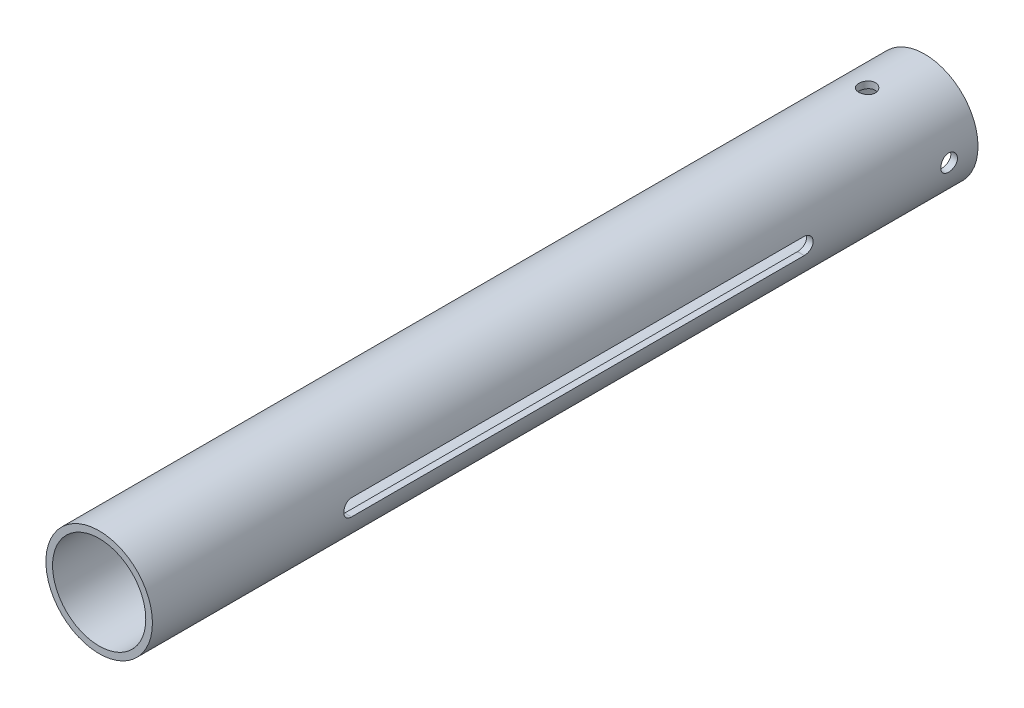
SolidWorks part; units mm, degrees
material "AISI 1010 Steel, hot rolled bar"
ref_plane "Front Plane" through (0, 0, 0) normal (0, 0, 1) x (1, 0, 0)
ref_plane "Top Plane" through (0, 0, 0) normal (0, 1, 0) x (1, 0, 0)
ref_plane "Right Plane" through (0, 0, 0) normal (1, 0, 0) x (0, 0, -1)
sketch "Sketch1" plane through (0, 0, 0) normal (0, 0, 1) x (1, 0, 0)
  line L0 (-25.4, 0) -> (-22.225, 0) construction
  circle A0 centre (0, 0) radius 22.225 construction
  circle A1 centre (0, 0) radius 25.4 construction
  dimension "OD" = 50.8
  dimension "ID" = 44.45
  dimension "Wall Thickness" = 3.175
sketch "Sketch2" plane through (0, 0, 0) normal (1, 0, 0) x (0, 0, -1)
  line L0 (-152.4, -25.4) -> (152.4, -25.4) construction
  point P2 (0, -25.4)
  point P3 (76.2, -25.4)
  point P4 (-76.2, -25.4)
  dimension "Length" = 304.8
  dimension "D1" = 76.2
  dimension "D2" = 76.2
sketch "Sketch3" plane through (0, 0, 0) normal (0, 0, 1) x (1, 0, 0)
  circle A0 centre (0, 0) radius 22.225 construction
  circle A1 centre (0, 0) radius 25.4 construction
  circle A2 centre (0, 0) radius 22.225
  circle A3 centre (0, 0) radius 25.4
extrude "Boss-Extrude2" add sketch "Sketch3" along normal up to vertex (152.4 mm away) and the other way up to vertex (152.4 mm away) up to point (0, -25.4, 152.4) other way up to point (0, -25.4, -152.4)
sketch "Sketch4" plane through (0, 0, 152.4) normal (0, 0, 1) x (1, 0, 0)
  circle A0 centre (0, 0) radius 36.4857
extrude "Cut-Extrude1" [suppressed] cut sketch "Sketch4" against normal offset from surface (12.7 mm away) 12.7 up to face at (25.4, 0, 152.4)
sketch "Sketch9" plane through (0, 0, 152.4) normal (0, 0, 1) x (1, 0, 0)
  circle A0 centre (0, 0) radius 22.225
  circle A1 centre (0, 0) radius 25.4
extrude "Boss-Extrude3" add sketch "Sketch9" along normal blind 88.9
sketch "Sketch5" plane through (0, 0, 0) normal (1, 0, 0) x (0, 0, -1)
  line L0 (-38.1, 0) -> (69.85, 0) construction
  line L1 (-38.1, 0) -> (-146.05, 0) construction
  line L2 (-241.3, 0) -> (152.4, 0) construction
  line L3 (152.4, -25.4) -> (152.4, 25.4) construction
  line L5 (-146.05, 3.9687) -> (69.85, 3.9687)
  line L6 (69.85, -3.9687) -> (-146.05, -3.9687)
  line L7 (-38.1, 3.9687) -> (-38.1, -3.9687) construction
  line L8 (-241.3, 25.4) -> (-241.3, -25.4) construction
  circle A0 centre (-146.05, 0) radius 3.9687 construction
  arc A2 (-146.05, 3.9687) -> (-146.05, -3.9687) centre (-146.05, 0) ccw
  circle A4 centre (69.85, 0) radius 3.9688 construction
  arc A5 (69.85, 3.9687) -> (69.85, -3.9687) centre (69.85, 0) cw
  point P13 (-38.1, 3.9687)
  point P14 (-38.1, -3.9687)
  point P17 (-38.1, 0)
  dimension "D1" = 107.95
  dimension "D2" = 82.55
  dimension "D3" = 7.9375
extrude "Cut-Extrude2" cut sketch "Sketch5" against normal through all both and the other way through all
sketch "Sketch6" plane through (0, 0, 0) normal (1, 0, 0) x (0, 0, -1)
  line L0 (152.4, -25.4) -> (152.4, 25.4) construction
  line L1 (111.125, 0) -> (124.8833, 0) construction
  line L2 (124.8833, 0) -> (138.6417, 0) construction
  line L3 (138.6417, 0) -> (152.4, 0) construction
  circle A0 centre (138.6417, 0) radius 3.9687
  point P0 (111.125, 0)
  point P1 (124.8833, 0)
  point P2 (138.6417, 0)
  point P3 (152.4, 0)
  dimension "D2" = 7.9375
  dimension "D1" = 41.275
extrude "Cut-Extrude3" cut sketch "Sketch6" against normal through all both and the other way through all
sketch "Sketch8" plane through (0, 0, 0) normal (0, 1, 0) x (1, 0, 0)
  line L1 (0, 111.125) -> (0, 124.8833) construction
  line L2 (0, 124.8833) -> (0, 138.6417) construction
  line L3 (0, 138.6417) -> (0, 152.4) construction
  line L4 (25.4, 152.4) -> (-25.4, 152.4) construction
  circle A1 centre (0, 124.8833) radius 3.9688
  point P0 (0, 111.125)
  point P1 (0, 124.8833)
  point P2 (0, 138.6417)
  point P3 (0, 152.4)
  dimension "D2" = 7.9375
  dimension "D1" = 41.275
extrude "Cut-Extrude4" cut sketch "Sketch8" against normal through all both and the other way through all
equation "\"D1@Sketch2\"=\"OD@Sketch1\"*1.5"
equation "\"D2@Sketch2\"=\"D1@Sketch2\""
